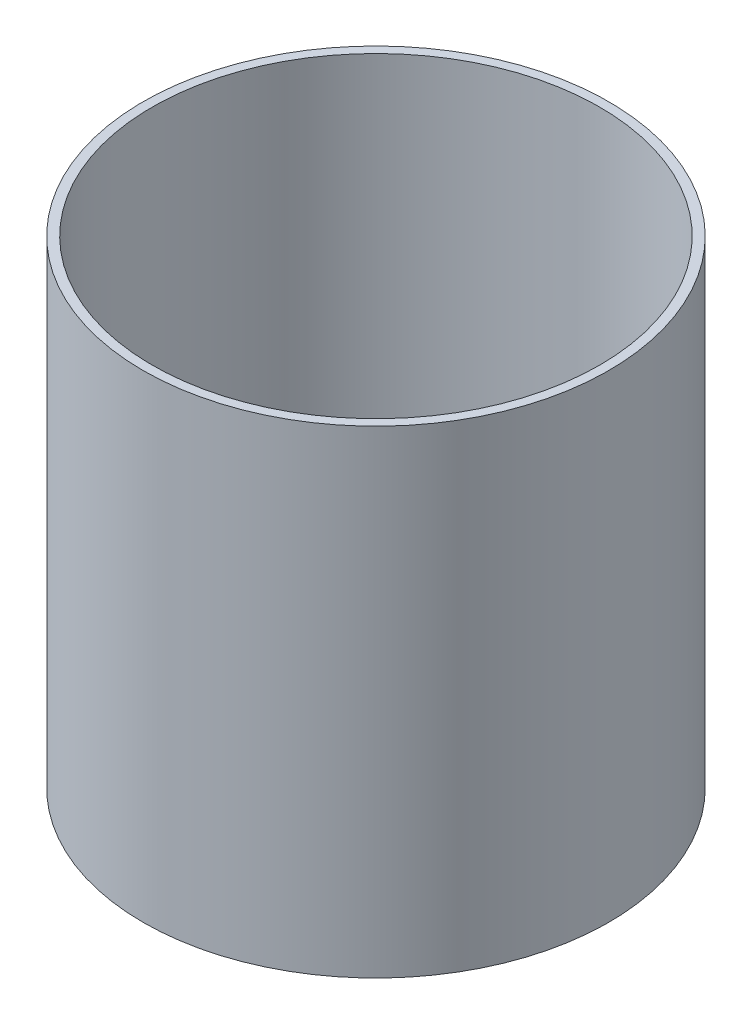
SolidWorks part; units mm, degrees
ref_plane "Front Plane" through (0, 0, 0) normal (0, 0, 1) x (1, 0, 0)
ref_plane "Top Plane" through (0, 0, 0) normal (0, 1, 0) x (1, 0, 0)
ref_plane "Right Plane" through (0, 0, 0) normal (1, 0, 0) x (0, 0, -1)
sketch "Sketch1" plane through (0, 0, 0) normal (0, 1, 0) x (1, 0, 0)
  circle A0 centre (0, 0) radius 38
  dimension "D1" = 76
extrude "Extrude-Thin1" add sketch "Sketch1" along normal blind 78 thin thin type one direction reverse wall 1.5
